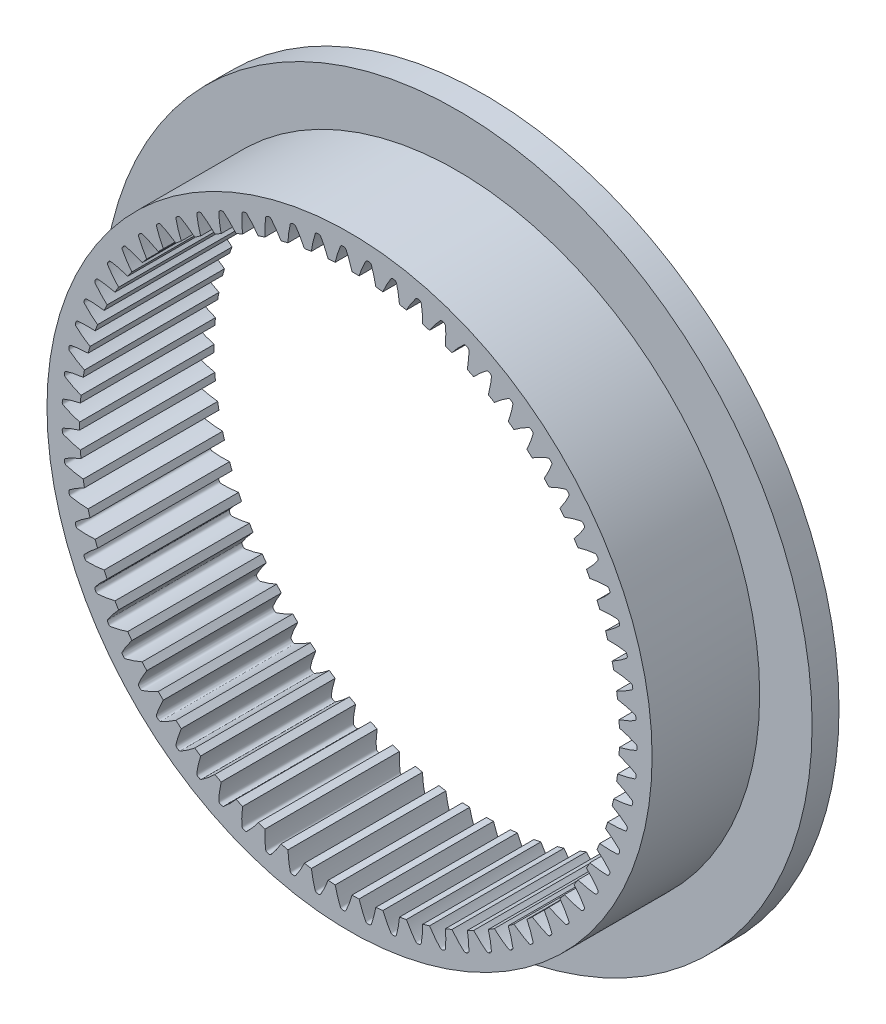
SolidWorks part; units mm, degrees
ref_plane "Front Plane" through (0, 0, 0) normal (0, 0, 1) x (1, 0, 0)
ref_plane "Top Plane" through (0, 0, 0) normal (0, 1, 0) x (1, 0, 0)
ref_plane "Right Plane" through (0, 0, 0) normal (1, 0, 0) x (0, 0, -1)
ref_axis "Axis1" through (0, 0, 55) along (0, 0, -1)
sketch "SketchRevolveRing_Gear_Follower02" plane through (0, 0, 0) normal (1, 0, 0) x (0, 0, -1)
  line L0 (0, 0) -> (25.4, 0) construction
  line L1 (-6.35, 25.4945) -> (-6.35, 38.1)
  line L2 (-6.35, 38.1) -> (6.35, 38.1)
  line L3 (6.35, 38.1) -> (6.35, 25.4945)
  line L4 (6.35, 25.4945) -> (-6.35, 25.4945)
  dimension "Side1" = 6.35
  dimension "OutsideRadius" = 38.1
  dimension "Side2" = 6.35
  dimension "MinorDiameter" = 25.4945
revolve "Ring_Gear_Follower02" add sketch "SketchRevolveRing_Gear_Follower02" angle 360 about L0
sketch "SketchToothRing_Gear_Follower02" plane through (0, 0, 0) normal (0, 0, 1) x (1, 0, 0)
  arc A0 (25.3229, -0.8287) -> (25.3229, 0.8287) centre (0, 0) ccw
  spline S0 degree 3 poles (25.3229, 0.8287) (25.4112, 0.8108) (25.5484, 0.7796) (25.737, 0.7307) (25.8937, 0.6865) (26.06, 0.6358) (26.2357, 0.5781) (26.4206, 0.513) (26.6146, 0.4404) (26.8165, 0.3579) (26.9656, 0.2993) (27.0537, 0.2557) (27.0798, 0.2362) (27.1027, 0.2137) (27.1221, 0.1881) (27.1375, 0.1599) (27.1526, 0.1203) (27.1579, 0.0772) (27.157, 0.0338) (27.1573, 0) (27.157, -0.0338) (27.1579, -0.0772) (27.1526, -0.1203) (27.1375, -0.1599) (27.1221, -0.1881) (27.1027, -0.2137) (27.0798, -0.2362) (27.0537, -0.2557) (26.9656, -0.2993) (26.8165, -0.3579) (26.6146, -0.4404) (26.4206, -0.513) (26.2357, -0.5781) (26.06, -0.6358) (25.8937, -0.6865) (25.737, -0.7307) (25.5484, -0.7796) (25.4112, -0.8108) (25.3229, -0.8287) knots 0 0 0 0 0.063805 0.09963 0.13807 0.179124 0.222794 0.269078 0.317977 0.369491 0.42362 0.431438 0.438996 0.446554 0.454113 0.461671 0.469229 0.484048 0.492024 0.5 0.507976 0.515952 0.530771 0.538329 0.545887 0.553446 0.561004 0.568562 0.57638 0.630509 0.682023 0.730922 0.777206 0.820876 0.86193 0.90037 0.936195 1 1 1 1
extrude "ToothExtrudeCutRing_Gear_Follower02" cut sketch "SketchToothRing_Gear_Follower02" against normal blind 6.35 and the other way blind 6.35
ref_axis "Axis2" through (41.91, 0, 0) along (-1, 0, 0)
ref_plane "Plane1" through (0, 0, 0) normal (0, 0, -1) x (1, 0, 0)
pattern_circular "PatternRing_Gear_Follower02" count 71 every 5.07 about axis through (0, 0, 55) along (0, 0, -1) of "ToothExtrudeCutRing_Gear_Follower02"
sketch "AuxiliarySketchRing_Gear_Follower02" plane through (0, 0, 0) normal (0, 0, 1) x (1, 0, 0)
  circle A0 centre (0, 0) radius 26.2335 construction
  circle A1 centre (0, 0) radius 24.6514 construction
  circle A2 centre (0, 0) radius 27.1572 construction
  circle A3 centre (0, 0) radius 25.4945 construction
  dimension "PitchDiameter" = 52.467
  dimension "BaseDiameter" = 49.3028
  dimension "MajorDiameter" = 54.3144
  dimension "MinorDiameter" = 50.989
sketch "Sketch1" plane through (0, 0, 6.35) normal (0, 0, 1) x (1, 0, 0)
  circle A0 centre (0, 0) radius 28.575
  circle A1 centre (0, 0) radius 38.1
  dimension "D1" = 57.15
  dimension "D2" = 76.2
extrude "Cut-Extrude1" cut sketch "Sketch1" against normal blind 10.16
sketch "Sketch2" plane through (0, 0, -3.81) normal (0, 0, 1) x (1, 0, 0)
  circle A0 centre (0, 0) radius 33.528
  circle A1 centre (0, 0) radius 38.1
  dimension "D1" = 67.056
  dimension "D2" = 76.2
extrude "Cut-Extrude2" cut sketch "Sketch2" against normal through all
